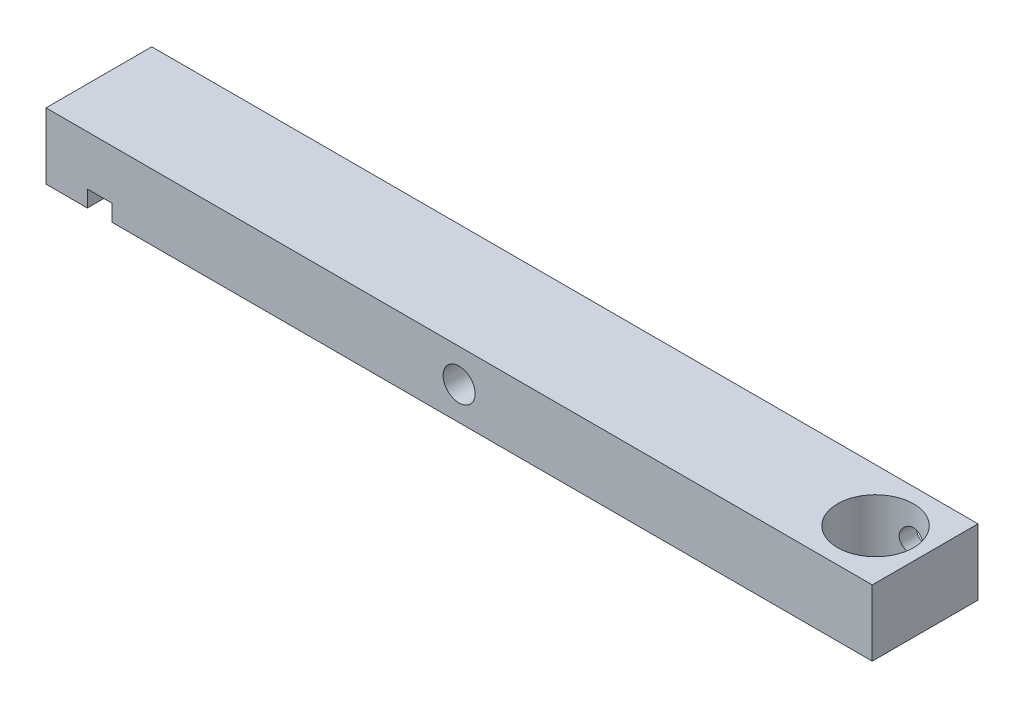
SolidWorks part; units mm, degrees
ref_plane "Front Plane" through (0, 0, 0) normal (0, 0, 1) x (1, 0, 0)
ref_plane "Top Plane" through (0, 0, 0) normal (0, 1, 0) x (1, 0, 0)
ref_plane "Right Plane" through (0, 0, 0) normal (1, 0, 0) x (0, 0, -1)
sketch "Sketch1" plane through (0, 0, 0) normal (0, 0, 1) x (1, 0, 0)
  line L1 (-63.5, -5.08) -> (63.5, -5.08)
  line L2 (-63.5, -5.08) -> (-63.5, 5.08)
  line L3 (-63.5, 5.08) -> (63.5, 5.08)
  line L4 (63.5, -5.08) -> (63.5, 5.08)
  line L5 (-63.5, -5.08) -> (63.5, 5.08) construction
  line L6 (-63.5, 5.08) -> (63.5, -5.08) construction
  point P0 (0, 0)
  dimension "D1" = 10.16
  dimension "D2" = 127
extrude "Boss-Extrude1" add sketch "Sketch1" along normal mid plane 16.256
hole_wizard "#10 (0.1935) Diameter Hole2" positions "Sketch4" profile "Sketch5" hole size "#10" standard "ANSI Inch" end condition through all
sketch "Sketch4" plane through (0, 0, 8.128) normal (0, 0, 1) x (1, 0, 0)
  point P0 (0, 0)
  point P3 (0, 0)
  point P5 (0, 0)
  point P6 (0, 0)
sketch "Sketch5" plane through (0, 0, 8.128) normal (1, 0, 0) x (0, -1, 0)
  line L0 (0, 0) -> (0, 16.256)
  line L1 (0, 16.256) -> (2.4574, 16.256)
  line L2 (2.4574, 16.256) -> (2.4574, 0)
  line L5 (2.4574, 0) -> (0, 0)
  line L11 (0, -6.35) -> (0, 107.95) construction
  dimension "Thru Hole Dia." = 4.9149
  dimension "Thru Hole Depth" = 16.256
sketch "Sketch6" plane through (0, 0, 8.128) normal (0, 0, 1) x (1, 0, 0)
  line L0 (-57.15, -5.08) -> (-57.15, -2.54)
  line L1 (-63.5, -5.08) -> (63.5, -5.08) construction
  line L2 (-57.15, -2.54) -> (-53.34, -2.54)
  line L3 (-53.34, -2.54) -> (-53.34, -5.08)
  line L4 (-57.15, -5.08) -> (-53.34, -5.08)
  dimension "D1" = 53.34
  dimension "D2" = 2.54
  dimension "D3" = 57.15
extrude "Cut-Extrude1" cut sketch "Sketch6" against normal up to surface (16.256 mm away) up to face at (2.4574, 0, -8.128)
hole_wizard "Hole1" positions "Sketch7" profile "Sketch8" legacy end condition through all
sketch "Sketch7" plane through (0, 5.08, 0) normal (0, 1, 0) x (1, 0, 0)
  point P0 (55.88, 0)
  point P3 (0, 0)
  point P5 (0, 0)
  dimension "D1" = 55.88
sketch "Sketch8" plane through (55.88, 5.08, 0) normal (1, 0, 0) x (0, 0, 1)
  line L0 (0, 0) -> (0, 10.16)
  line L1 (0, 10.16) -> (5.842, 10.16)
  line L2 (5.842, 10.16) -> (5.842, 0)
  line L3 (5.842, 0) -> (0, 0)
  line L4 (0, 110) -> (0, -10) construction
  dimension "Diameter" = 11.684
  dimension "Depth" = 10.16
hole_wizard "#25 (0.1495) Diameter Hole1" positions "Sketch9" profile "Sketch11" hole size "#25" standard "ANSI Inch"
sketch "Sketch9" plane through (0, 0, -8.128) normal (0, 0, -1) x (-1, 0, 0)
  point P0 (-55.88, 0)
  dimension "D1" = 55.88
sketch "Sketch11" plane through (55.88, 0, -8.128) normal (1, 0, 0) x (0, 1, 0)
  line L0 (0, 0) -> (0, 8.127)
  line L1 (0, 8.127) -> (1.8986, 6.9862)
  line L2 (1.8986, 6.9862) -> (1.8986, 0)
  line L5 (1.8986, 0) -> (0, 0)
  line L10 (0, 8.127) -> (-1.8987, 6.9862) construction
  line L11 (0, -6.35) -> (0, 107.95) construction
  dimension "Hole Dia." = 3.7973
  dimension "Hole Depth" = 8.127
  dimension "Drill Angle" = 118
